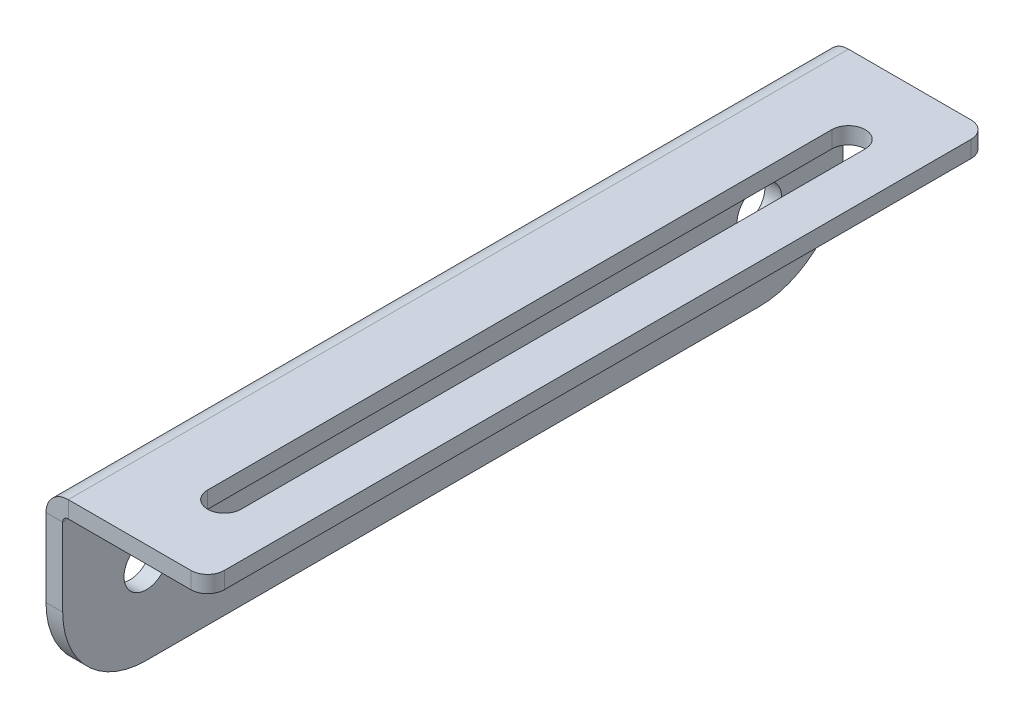
SolidWorks part; units mm, degrees
note: The reader was unsure of these and kept them because the rebuilt part matched: flange length of "Edge-Flange1".
ref_plane "Front Plane" through (0, 0, 0) normal (0, 0, 1) x (1, 0, 0)
ref_plane "Top Plane" through (0, 0, 0) normal (0, 1, 0) x (1, 0, 0)
ref_plane "Right Plane" through (0, 0, 0) normal (1, 0, 0) x (0, 0, -1)
sketch "Sketch1" plane through (0, 0, 0) normal (0, 1, 0) x (1, 0, 0)
  line L0 (-14.5, 0) -> (14.5, 0) construction
  line L1 (-14.5, 70) -> (11.5, 70)
  line L2 (-14.5, 70) -> (-14.5, -70)
  line L3 (-14.5, -70) -> (11.5, -70)
  line L4 (14.5, 67) -> (14.5, -67)
  line L5 (-14.5, 70) -> (14.5, -70) construction
  line L6 (-14.5, -70) -> (14.5, 70) construction
  line L7 (3.5, 56) -> (3.5, -56) construction
  line L8 (6.5, 56) -> (6.5, -56)
  line L9 (0.5, 56) -> (0.5, -56)
  arc A0 (6.5, 56) -> (0.5, 56) centre (3.5, 56) ccw
  arc A1 (0.5, -56) -> (6.5, -56) centre (3.5, -56) ccw
  arc A2 (11.5, -70) -> (14.5, -67) centre (11.5, -67) ccw
  arc A3 (11.5, 70) -> (14.5, 67) centre (11.5, 67) cw
  point P0 (0, 0)
  point P10 (3.5, 0)
  dimension "D6" = 3
  dimension "D1" = 140
  dimension "D2" = 6
  dimension "D3" = 18
  dimension "D4" = 8
  dimension "D5" = 14
base flange "Base-Flange1" sketch "Sketch1" thickness 3 reverse thickness direction no parameters "D1"=0.7366
edge flange "Edge-Flange1" sketch "Sketch14" flange angle 90 flange length 30 flange position material inside bend radius 1 thickness 3 relief rectangular parameters "D6"=10
bend "EdgeBend2" bend radius 1 bend angle 90 parameters "D5"=1
sketch "Sketch14" plane through (-14.5, -3, 0) normal (-1, 0, 0) x (0, 0, -1)
  line L0 (70, 0) -> (-70, 0) construction
  line L1 (70, 0) -> (-70, 0)
  line L2 (-70, 0) -> (-70, 30)
  line L3 (-70, 30) -> (70, 30)
  line L4 (70, 30) -> (70, 0)
sketch "Sketch10" plane through (-14.5, 0, 0) normal (-1, 0, 0) x (0, 0, 1)
  line L0 (-70, -18) -> (70, -18) construction
  line L3 (-70, -33) -> (70, -33) construction
  line L4 (0, -3) -> (0, -33) construction
  line L8 (-70, -4) -> (-70, -33) construction
  line L9 (-70, -3) -> (70, -3) construction
  line L10 (-70, -18) -> (-70, -33)
  line L11 (-70, -33) -> (-55, -33)
  line L12 (70, -33) -> (55, -33)
  line L13 (70, -18) -> (70, -33)
  circle A0 centre (-55, -18) radius 4
  circle A1 centre (-55, -18) radius 15
  circle A2 centre (55, -18) radius 4
  circle A3 centre (55, -18) radius 15
  point P3 (0, -18)
  dimension "D1" = 8
  dimension "D2" = 110
extrude "Cut-Extrude1" cut sketch "Sketch10" against normal up to next
sketch "Bend-Lines1" [suppressed] plane through (0, 0, 0) normal (0, 1, 0) x (1, 0, 0)
sketch "Bounding-Box1" [suppressed] plane through (0, 0, 0) normal (0, 1, 0) x (1, 0, 0)
sheet metal parameters "Sheet-Metal2" thickness 3 parameters "D1"=0.7366
flat pattern "Flat-Pattern2" [suppressed]
sketch "Bend-Lines2" plane through (0, 0, 0) normal (0, 1, 0) x (1, 0, 0)
sketch3d "Bounding-Box2" [suppressed]
  line L0 (14.5, 70, 0) -> (14.5, -70, 0) construction
  line L1 (-14.5, 70, 0) -> (-14.5, -70, 0) construction
  line L2 (14.5, 70, 0) -> (-14.5, 70, 0) construction
  line L3 (14.5, -70, 0) -> (-14.5, -70, 0) construction
sheet metal parameters "Sheet-Metal3" thickness 3 parameters "D1"=0.7366
flat pattern "Flat-Pattern2" [suppressed]
sketch "Bend-Lines2" plane through (0, 0, 0) normal (0, 1, 0) x (1, 0, 0)
  line L2 (-12.4635, 70) -> (-12.4635, -70) construction
  line L3 (-12.4635, 70) -> (-12.4635, -70) construction
sketch3d "Bounding-Box2" [suppressed]
  line L0 (-43.427, 70, 0) -> (-43.427, -70, 0) construction
  line L1 (14.5, 70, 0) -> (14.5, -70, 0) construction
  line L2 (-43.427, 70, 0) -> (14.5, 70, 0) construction
  line L3 (-43.427, -70, 0) -> (14.5, -70, 0) construction
bend of the flat pattern "Flatten-<EdgeBend2>1"
sketch "Sketch10-1" [suppressed] plane through (-10.427, 0, 0) normal (0, 1, 0) x (0, 0, 1)
  line L0 (-70, -18) -> (70, -18) construction
  line L4 (0, -3) -> (0, -33) construction
  circle A0 centre (-55, -18) radius 4
  circle A1 centre (-55, -18) radius 15
  circle A2 centre (55, -18) radius 4
  circle A3 centre (55, -18) radius 15
  dimension "D1" = 8
  dimension "D2" = 110
sheet metal parameters "Sheet-Metal4" thickness 3 parameters "D1"=0.7366
flat pattern "Flat-Pattern2" [suppressed]
sketch "Bend-Lines2" plane through (0, 0, 0) normal (0, 1, 0) x (1, 0, 0)
  line L2 (-12.4635, 70) -> (-12.4635, -70) construction
  line L3 (-12.4635, 70) -> (-12.4635, -70) construction
sketch3d "Bounding-Box2" [suppressed]
  line L0 (3, 137, 0) -> (3, -3, 0) construction
  line L1 (-54.927, 137, 0) -> (-54.927, -3, 0) construction
  line L2 (3, 137, 0) -> (-54.927, 137, 0) construction
  line L3 (3, -3, 0) -> (-54.927, -3, 0) construction
bend of the flat pattern "Flatten-<EdgeBend2>1"
sketch "Sketch10-1" plane through (-10.427, 0, 0) normal (0, 1, 0) x (0, 0, 1)
  line L0 (-70, -18) -> (70, -18) construction
  line L4 (0, -3) -> (0, -33) construction
  line L10 (-70, -18) -> (-70, -33)
  line L11 (-70, -33) -> (-55, -33)
  line L12 (70, -33) -> (55, -33)
  line L13 (70, -18) -> (70, -33)
  circle A0 centre (-55, -18) radius 4
  circle A1 centre (-55, -18) radius 15
  circle A2 centre (55, -18) radius 4
  circle A3 centre (55, -18) radius 15
  dimension "D1" = 8
  dimension "D2" = 110
